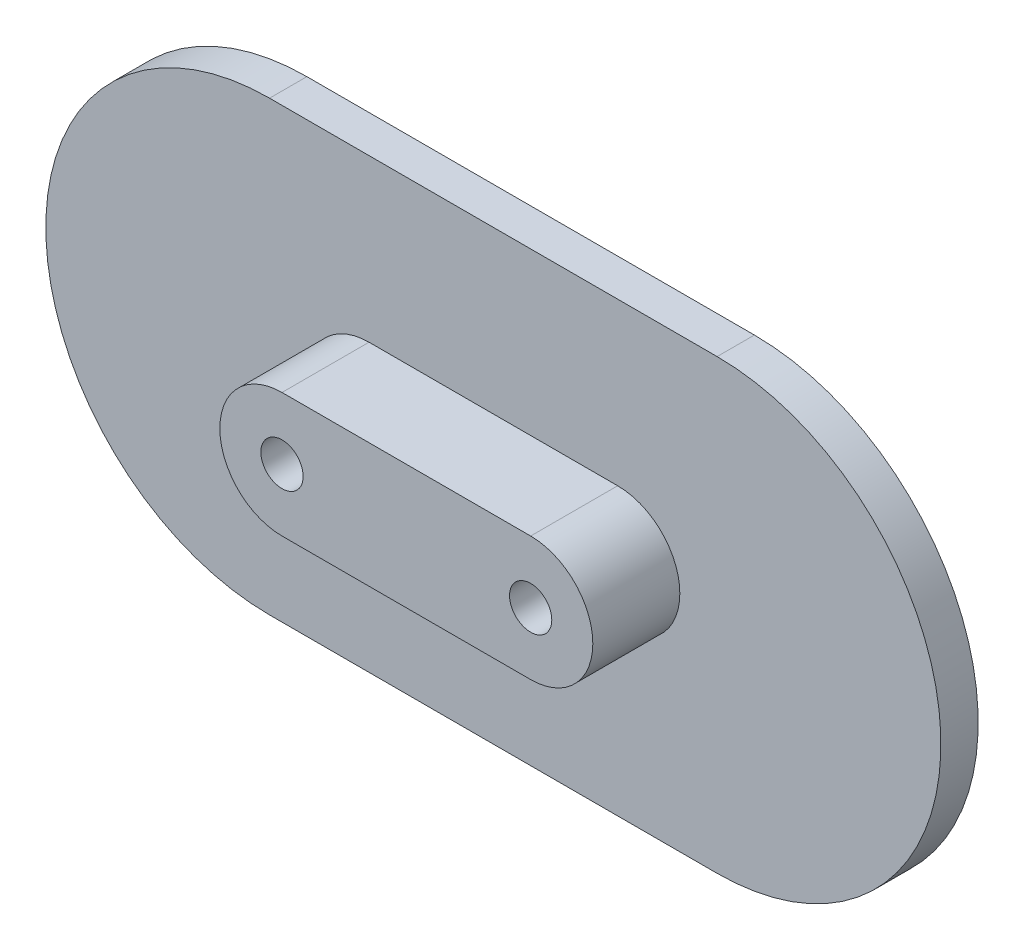
SolidWorks part; units mm, degrees
ref_plane "前视基准面" through (0, 0, 0) normal (0, 0, 1) x (1, 0, 0)
ref_plane "上视基准面" through (0, 0, 0) normal (0, 1, 0) x (1, 0, 0)
ref_plane "右视基准面" through (0, 0, 0) normal (1, 0, 0) x (0, 0, -1)
sketch "草图1" plane through (0, 0, 0) normal (0, 0, 1) x (1, 0, 0)
  line L0 (-18, 0) -> (18, 0) construction
  line L1 (-18, 18) -> (18, 18)
  line L2 (-18, -18) -> (18, -18)
  line L3 (-10, 0) -> (10, 0) construction
  line L4 (-10, 5) -> (10, 5)
  line L5 (-10, -5) -> (10, -5)
  arc A0 (-18, 18) -> (-18, -18) centre (-18, 0) ccw
  arc A1 (18, -18) -> (18, 18) centre (18, 0) ccw
  circle A2 centre (-10, 0) radius 1.7
  circle A3 centre (10, 0) radius 1.7
  arc A4 (-10, 5) -> (-10, -5) centre (-10, 0) ccw
  arc A5 (10, -5) -> (10, 5) centre (10, 0) ccw
  circle A6 centre (-10, 0) radius 3.2
  circle A7 centre (10, 0) radius 3.2
  point P3 (0, 0)
  point P12 (0, 0)
  dimension "D1" = 3.4
  dimension "D2" = 3.4
  dimension "D3" = 10
  dimension "D4" = 10
  dimension "D5" = 18
  dimension "D7" = 5
  dimension "D6" = 36
extrude "凸台-拉伸1" add sketch "草图1" along normal blind 3 contours L2 A1 L1 A0 A5 L5 A4 L4 region at (0, 17.195, 0)
extrude "凸台-拉伸2" add sketch "草图1<3>" along normal blind 10 contours L5 A5 L4 A4 A7 A6 | A6 A2 | A7 A3 region at (0, 0, 0) region at (-13.1095, 0, 0) region at (6.8905, 0, 0)
sketch "草图1<3>" plane through (0, 0, 0) normal (0, 0, 1) x (1, 0, 0) same geometry as "草图1"
chamfer "倒角1" distance 1.4 angle 45 2 edges at (11.7, 0, 0) (-8.3, 0, 0)
